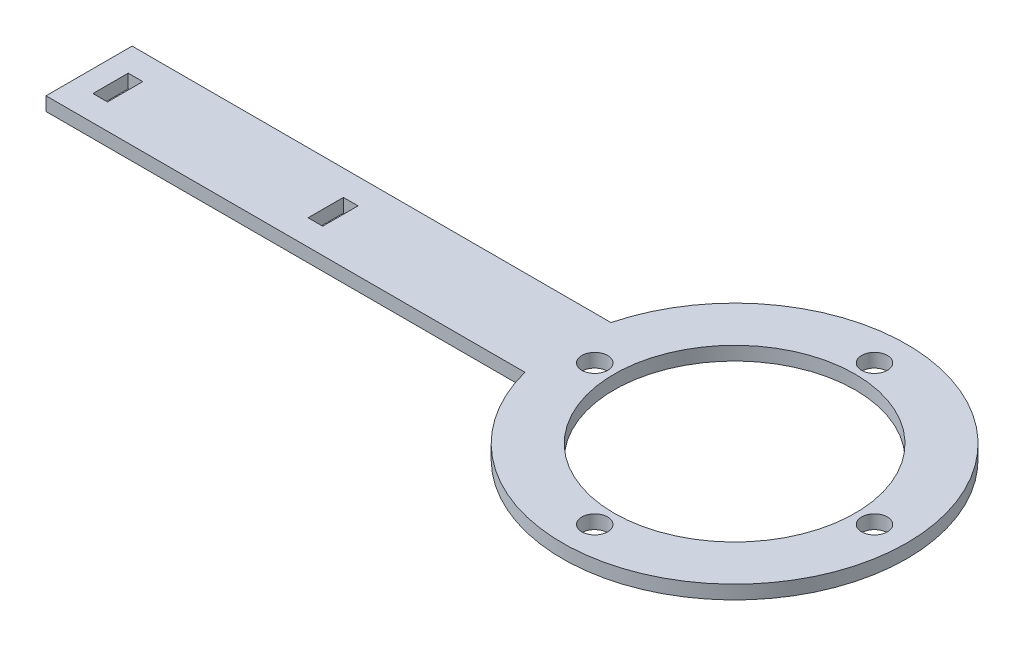
SolidWorks part; units mm, degrees
ref_plane "Front Plane" through (0, 0, 0) normal (0, 0, 1) x (1, 0, 0)
ref_plane "Top Plane" through (0, 0, 0) normal (0, 1, 0) x (1, 0, 0)
ref_plane "Right Plane" through (0, 0, 0) normal (1, 0, 0) x (0, 0, -1)
sketch "Sketch1" plane through (0, 0, 0) normal (0, 1, 0) x (1, 0, 0)
  line L0 (-38.7298, 0) -> (-145, 0) construction
  line L5 (-145, 4.1) -> (-141.6, 4.1)
  line L6 (-141.6, 4.1) -> (-141.6, -4.1)
  line L7 (-38.7298, -10) -> (-145, -10)
  line L8 (-38.7298, 10) -> (-145, 10)
  line L9 (-38.7298, 0) -> (0, 0) construction
  line L10 (-141.6, -4.1) -> (-145, -4.1)
  line L14 (-38.7298, 10) -> (-38.7298, -10) construction
  line L15 (-145, 10) -> (-145, -10) construction
  line L16 (-150, 0) -> (-145, 0) construction
  line L17 (0, 32.5) -> (0, 0) construction
  line L18 (0, 0) -> (32.5, 0) construction
  line L19 (-145, 10) -> (-150, 10)
  line L20 (0, -32.5) -> (0, 0) construction
  line L21 (-150, 10) -> (-150, -10)
  line L22 (-150, -10) -> (-145, -10)
  line L23 (-145, 4.1) -> (-145, -4.1)
  line L25 (-91.6, -4.1) -> (-91.6, 4.1)
  line L27 (-91.6, 4.1) -> (-95, 4.1)
  line L28 (-95, 4.1) -> (-95, -4.1)
  line L29 (-95, -4.1) -> (-91.6, -4.1)
  circle A0 centre (0, 0) radius 28
  circle A1 centre (0, 0) radius 32.5 construction
  circle A2 centre (0, 32.5) radius 3
  circle A3 centre (-32.5, 0) radius 3
  circle A4 centre (0, -32.5) radius 3
  circle A5 centre (32.5, 0) radius 3
  circle A11 centre (0, 0) radius 40
  point P3 (-140.3966, 3.873)
  point P17 (-120.1072, 10)
  point P25 (-130.2914, 5.6928)
  point P27 (0, 0)
  dimension "D1" = 56
  dimension "D2" = 65
  dimension "D5" = 6
  dimension "D3" = 80
  dimension "D4" = 3.4
  dimension "D6" = 5
  dimension "D7" = 20
  dimension "D8" = 8.2
  dimension "D9" = 50
  dimension "D12" = 150
extrude "Boss-Extrude1" add sketch "Sketch1" along normal blind 3.175 contours A11 L8 L19 L21 L22 L7 L23 L5 L6 L10 L29 L28 L27 L25 | A11 A5 A4 A3 A2 A0 region at (-91.8649, 0, 8.8695) region at (-38.8686, 0, 0)
